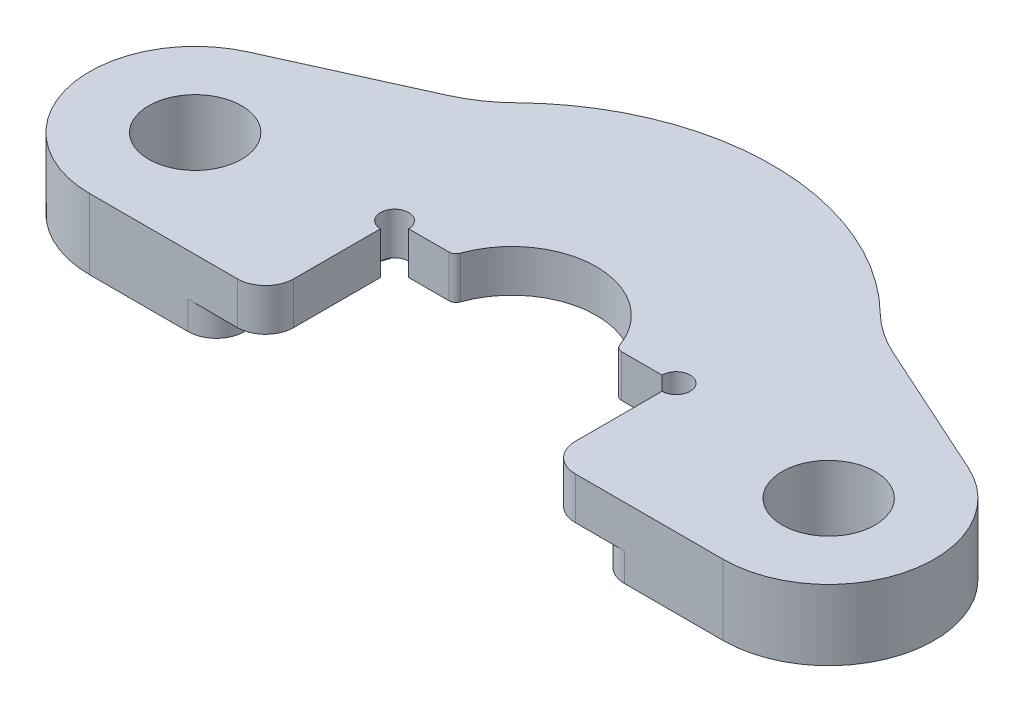
SolidWorks part; units mm, degrees
ref_plane "Front Plane" through (0, 0, 0) normal (0, 0, 1) x (1, 0, 0)
ref_plane "Top Plane" through (0, 0, 0) normal (0, 1, 0) x (1, 0, 0)
ref_plane "Right Plane" through (0, 0, 0) normal (1, 0, 0) x (0, 0, -1)
sketch "Sketch1" plane through (0, 0, 0) normal (0, 1, 0) x (1, 0, 0)
  line L0 (-25.5905, 6.8336) -> (-14.0253, 12.0641)
  line L5 (25.5905, 6.8336) -> (14.0253, 12.0641)
  line L7 (22.5, -7.5) -> (-22.5, -7.5)
  arc A0 (14.0253, 12.0641) -> (-14.0253, 12.0641) centre (0, 0) ccw
  arc A7 (-25.5905, 6.8336) -> (-22.5, -7.5) centre (-22.5, 0) ccw
  arc A9 (22.5, -7.5) -> (25.5905, 6.8336) centre (22.5, 0) ccw
  point P1 (0, 0)
  point P3 (0, 0)
  point P8 (0, 0)
  point P9 (-13.9306, 12.1732)
  point P10 (14.0253, 12.0641)
  point P23 (0, 0)
  point P24 (-12.8659, 12.5884)
  point P25 (0, 0)
  dimension "D1" = 15
extrude "Boss-Extrude1" add sketch "Sketch1" along normal blind 5
sketch "Sketch2" plane through (0, 5, 0) normal (0, 1, 0) x (1, 0, 0)
  line L0 (10, -7.5) -> (10, 1.6615)
  line L3 (-22.5, -7.5) -> (22.5, -7.5) construction
  line L4 (10, 1.6615) -> (5.7654, 1.6615)
  line L5 (-5.7654, 1.6615) -> (-10, 1.6615)
  line L6 (-10, 1.6615) -> (-10, -7.5)
  line L7 (-10, -7.5) -> (10, -7.5)
  arc A3 (5.7654, 1.6615) -> (-5.7654, 1.6615) centre (0, 0) ccw
  point P2 (0, 0)
  point P4 (8.9522, 1.6855)
  point P12 (-6.2233, 0)
  point P13 (-6.0526, 2.0482)
  point P14 (5.7654, 1.6615)
  point P15 (0, 0)
  point P16 (0, 0)
  point P17 (0, 0)
  dimension "D3" = 6
extrude "Cut-Extrude1" cut sketch "Sketch2" against normal through all
fillet "Fillet1" radius 10 2 edges at (-14.0253, 2.5, -12.0641) (14.0253, 2.5, -12.0641)
hole_wizard "M6 Clearance Hole1" positions "Sketch3" profile "Sketch4" hole size "M6" standard "ANSI Metric" end condition through all
sketch "Sketch3" plane through (0, 5, 0) normal (0, 1, 0) x (1, 0, 0)
  point P0 (-22.5, 0)
  point P3 (22.5, 0)
sketch "Sketch4" plane through (-22.5, 5, 0) normal (1, 0, 0) x (0, 0, 1)
  line L0 (0, 0) -> (0, 5)
  line L1 (0, 5) -> (3.3, 5)
  line L2 (3.3, 5) -> (3.3, 0)
  line L5 (3.3, 0) -> (0, 0)
  line L11 (0, -6.35) -> (0, 107.95) construction
  dimension "Thru Hole Dia." = 6.6
  dimension "Thru Hole Depth" = 5
fillet "Fillet2" radius 0.5 2 edges at (5.7654, 2.5, -1.6615) (-5.7654, 2.5, -1.6615)
sketch "Sketch5" plane through (0, 5, 0) normal (0, 1, 0) x (1, 0, 0)
  circle A0 centre (-10, 1.6615) radius 1
  circle A1 centre (10, 1.6615) radius 1
  dimension "D1" = 2
extrude "Cut-Extrude2" cut sketch "Sketch5" against normal through all
fillet "Fillet3" radius 2 2 edges at (10, 2.5, 7.5) (-10, 2.5, 7.5)
sketch "Sketch6" plane through (0, 0, 0) normal (0, -1, 0) x (1, 0, 0)
  line L0 (0, 0) -> (0, 12) construction
  line L1 (-13.5, 0) -> (-13.5, 12)
  line L2 (13.5, 0) -> (13.5, 12)
  arc A1 (-13.5, 0) -> (13.5, 0) centre (0, 0) ccw
  arc A2 (13.5, 12) -> (-13.5, 12) centre (0, 12) ccw
  point P3 (0, 6)
  dimension "D1" = 12
  dimension "D2" = 27
extrude "Cut-Extrude3" cut sketch "Sketch6" against normal blind 2
fillet "Fillet4" radius 2 2 edges at (-13.5, 1, 7.5) (13.5, 1, 7.5)
